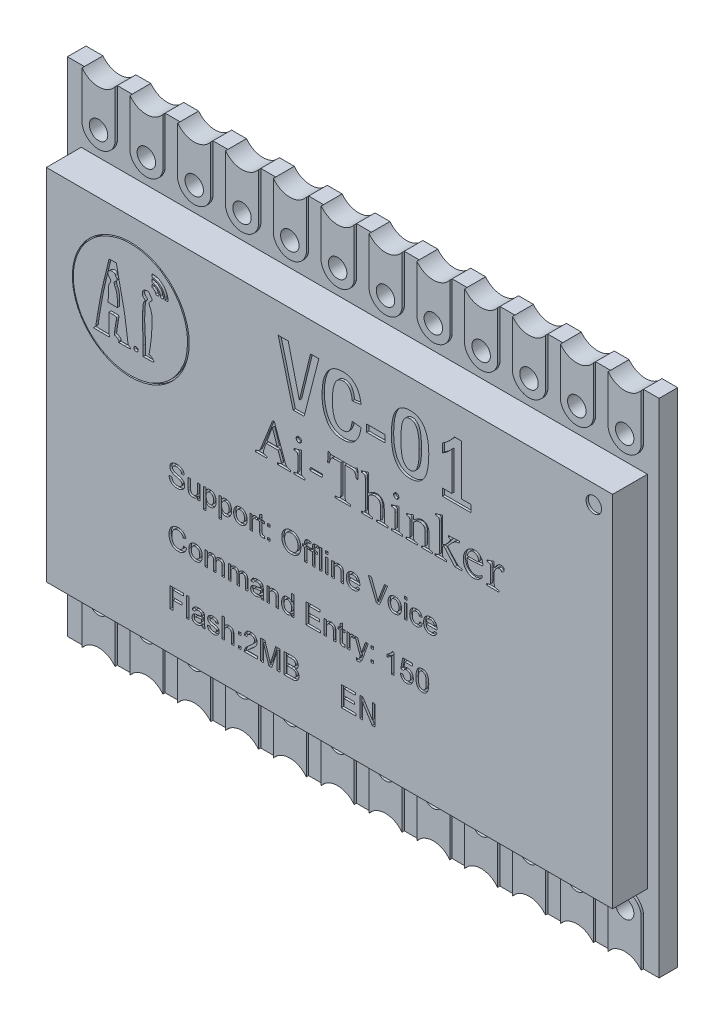
SolidWorks part; units mm, degrees
material "1.4000 (X6Cr13)"
ref_plane "Plan de face" through (0, 0, 0) normal (0, 0, 1) x (1, 0, 0)
ref_plane "Plan de dessus" through (0, 0, 0) normal (0, 1, 0) x (1, 0, 0)
ref_plane "Plan de droite" through (0, 0, 0) normal (1, 0, 0) x (0, 0, -1)
sketch "Esquisse4" plane through (0, 0, 0) normal (0, 0, 1) x (1, 0, 0)
  line L0 (5.9792, 122.5699) -> (31.4792, 122.5699) construction
  line L1 (6.698, 120.6494) -> (30.8117, 120.6494) construction
  line L2 (5.9667, 122.741) -> (6.698, 122.741)
  line L3 (5.9667, 122.741) -> (5.9667, 101.1199)
  line L4 (8.1154, 101.1199) -> (8.758, 101.1199)
  line L5 (31.4487, 122.741) -> (31.4487, 101.1199)
  line L6 (6.698, 122.741) -> (6.698, 120.6494)
  line L7 (8.1154, 122.741) -> (8.1154, 120.6494)
  line L8 (8.1154, 122.741) -> (8.758, 122.741)
  line L9 (10.1754, 122.741) -> (10.1754, 120.6494)
  line L10 (8.758, 122.741) -> (8.758, 120.6494)
  line L11 (12.2354, 122.741) -> (12.2354, 120.6494)
  line L12 (10.818, 122.741) -> (10.818, 120.6494)
  line L13 (14.2954, 122.741) -> (14.2954, 120.6494)
  line L14 (12.878, 122.741) -> (12.878, 120.6494)
  line L15 (16.3554, 122.741) -> (16.3554, 120.6494)
  line L16 (14.938, 122.741) -> (14.938, 120.6494)
  line L17 (18.4154, 122.741) -> (18.4154, 120.6494)
  line L18 (16.998, 122.741) -> (16.998, 120.6494)
  line L19 (20.4754, 122.741) -> (20.4754, 120.6494)
  line L20 (19.058, 122.741) -> (19.058, 120.6494)
  line L21 (22.5354, 122.741) -> (22.5354, 120.6494)
  line L22 (21.118, 122.741) -> (21.118, 120.6494)
  line L23 (24.5954, 122.741) -> (24.5954, 120.6494)
  line L24 (23.178, 122.741) -> (23.178, 120.6494)
  line L25 (26.6554, 122.741) -> (26.6554, 120.6494)
  line L26 (25.238, 122.741) -> (25.238, 120.6494)
  line L27 (28.7154, 122.741) -> (28.7154, 120.6494)
  line L28 (27.298, 122.741) -> (27.298, 120.6494)
  line L29 (30.7754, 122.741) -> (30.7754, 120.6494)
  line L30 (29.358, 122.741) -> (29.358, 120.6494)
  line L31 (10.1754, 122.741) -> (10.818, 122.741)
  line L32 (12.2354, 122.741) -> (12.878, 122.741)
  line L33 (14.2954, 122.741) -> (14.938, 122.741)
  line L34 (16.3554, 122.741) -> (16.998, 122.741)
  line L35 (18.4154, 122.741) -> (19.058, 122.741)
  line L36 (20.4754, 122.741) -> (21.118, 122.741)
  line L37 (22.5354, 122.741) -> (23.178, 122.741)
  line L38 (24.5954, 122.741) -> (25.238, 122.741)
  line L39 (26.6554, 122.741) -> (27.298, 122.741)
  line L40 (28.7154, 122.741) -> (29.358, 122.741)
  line L41 (30.7754, 122.741) -> (31.4487, 122.741)
  line L42 (5.9667, 111.9304) -> (31.4487, 111.9304) construction
  line L43 (8.1154, 101.1199) -> (8.1154, 103.2114)
  line L44 (6.698, 101.1199) -> (6.698, 103.2114)
  line L45 (8.758, 101.1199) -> (8.758, 103.2114)
  line L46 (10.1754, 101.1199) -> (10.1754, 103.2114)
  line L47 (10.818, 101.1199) -> (10.818, 103.2114)
  line L48 (12.2354, 101.1199) -> (12.2354, 103.2114)
  line L49 (12.878, 101.1199) -> (12.878, 103.2114)
  line L50 (14.2954, 101.1199) -> (14.2954, 103.2114)
  line L51 (14.938, 101.1199) -> (14.938, 103.2114)
  line L52 (16.3554, 101.1199) -> (16.3554, 103.2114)
  line L53 (16.998, 101.1199) -> (16.998, 103.2114)
  line L54 (18.4154, 101.1199) -> (18.4154, 103.2114)
  line L55 (19.058, 101.1199) -> (19.058, 103.2114)
  line L56 (20.4754, 101.1199) -> (20.4754, 103.2114)
  line L57 (21.118, 101.1199) -> (21.118, 103.2114)
  line L58 (22.5354, 101.1199) -> (22.5354, 103.2114)
  line L59 (23.178, 101.1199) -> (23.178, 103.2114)
  line L60 (24.5954, 101.1199) -> (24.5954, 103.2114)
  line L61 (25.238, 101.1199) -> (25.238, 103.2114)
  line L62 (26.6554, 101.1199) -> (26.6554, 103.2114)
  line L63 (27.298, 101.1199) -> (27.298, 103.2114)
  line L64 (28.7154, 101.1199) -> (28.7154, 103.2114)
  line L65 (29.358, 101.1199) -> (29.358, 103.2114)
  line L66 (30.7754, 101.1199) -> (30.7754, 103.2114)
  line L67 (10.1754, 101.1199) -> (10.818, 101.1199)
  line L68 (12.2354, 101.1199) -> (12.878, 101.1199)
  line L69 (14.2954, 101.1199) -> (14.938, 101.1199)
  line L70 (16.3554, 101.1199) -> (21.118, 101.1199)
  line L71 (22.5354, 101.1199) -> (23.178, 101.1199)
  line L72 (24.5954, 101.1199) -> (25.238, 101.1199)
  line L73 (26.6554, 101.1199) -> (27.298, 101.1199)
  line L74 (28.7154, 101.1199) -> (29.358, 101.1199)
  line L75 (30.7754, 101.1199) -> (31.4487, 101.1199)
  arc A0 (6.698, 122.741) -> (8.1154, 122.741) centre (7.4067, 123.281) ccw
  arc A1 (6.698, 120.6494) -> (8.1154, 120.6494) centre (7.4067, 120.7811) ccw
  circle A2 centre (7.4067, 120.7811) radius 0.3977
  arc A3 (8.758, 122.741) -> (10.1754, 122.741) centre (9.4667, 123.281) ccw
  arc A4 (8.758, 120.6494) -> (10.1754, 120.6494) centre (9.4667, 120.7811) ccw
  circle A5 centre (9.4667, 120.7811) radius 0.3977
  arc A6 (10.818, 122.741) -> (12.2354, 122.741) centre (11.5267, 123.281) ccw
  arc A7 (10.818, 120.6494) -> (12.2354, 120.6494) centre (11.5267, 120.7811) ccw
  circle A8 centre (11.5267, 120.7811) radius 0.3977
  arc A9 (12.878, 122.741) -> (14.2954, 122.741) centre (13.5867, 123.281) ccw
  arc A10 (12.878, 120.6494) -> (14.2954, 120.6494) centre (13.5867, 120.7811) ccw
  circle A11 centre (13.5867, 120.7811) radius 0.3977
  arc A12 (14.938, 122.741) -> (16.3554, 122.741) centre (15.6467, 123.281) ccw
  arc A13 (14.938, 120.6494) -> (16.3554, 120.6494) centre (15.6467, 120.7811) ccw
  circle A14 centre (15.6467, 120.7811) radius 0.3977
  arc A15 (16.998, 122.741) -> (18.4154, 122.741) centre (17.7067, 123.281) ccw
  arc A16 (16.998, 120.6494) -> (18.4154, 120.6494) centre (17.7067, 120.7811) ccw
  circle A17 centre (17.7067, 120.7811) radius 0.3977
  arc A18 (19.058, 122.741) -> (20.4754, 122.741) centre (19.7667, 123.281) ccw
  arc A19 (19.058, 120.6494) -> (20.4754, 120.6494) centre (19.7667, 120.7811) ccw
  circle A20 centre (19.7667, 120.7811) radius 0.3977
  arc A21 (21.118, 122.741) -> (22.5354, 122.741) centre (21.8267, 123.281) ccw
  arc A22 (21.118, 120.6494) -> (22.5354, 120.6494) centre (21.8267, 120.7811) ccw
  circle A23 centre (21.8267, 120.7811) radius 0.3977
  arc A24 (23.178, 122.741) -> (24.5954, 122.741) centre (23.8867, 123.281) ccw
  arc A25 (23.178, 120.6494) -> (24.5954, 120.6494) centre (23.8867, 120.7811) ccw
  circle A26 centre (23.8867, 120.7811) radius 0.3977
  arc A27 (25.238, 122.741) -> (26.6554, 122.741) centre (25.9467, 123.281) ccw
  arc A28 (25.238, 120.6494) -> (26.6554, 120.6494) centre (25.9467, 120.7811) ccw
  circle A29 centre (25.9467, 120.7811) radius 0.3977
  arc A30 (27.298, 122.741) -> (28.7154, 122.741) centre (28.0067, 123.281) ccw
  arc A31 (27.298, 120.6494) -> (28.7154, 120.6494) centre (28.0067, 120.7811) ccw
  circle A32 centre (28.0067, 120.7811) radius 0.3977
  arc A33 (29.358, 122.741) -> (30.7754, 122.741) centre (30.0667, 123.281) ccw
  arc A34 (29.358, 120.6494) -> (30.7754, 120.6494) centre (30.0667, 120.7811) ccw
  circle A35 centre (30.0667, 120.7811) radius 0.3977
  circle A36 centre (7.4067, 103.0797) radius 0.3977
  arc A37 (6.698, 103.2114) -> (8.1154, 103.2114) centre (7.4067, 103.0797) cw
  arc A38 (6.698, 101.1199) -> (8.1154, 101.1199) centre (7.4067, 100.5799) cw
  arc A39 (8.758, 101.1199) -> (10.1754, 101.1199) centre (9.4667, 100.5799) cw
  arc A40 (8.758, 103.2114) -> (10.1754, 103.2114) centre (9.4667, 103.0797) cw
  circle A41 centre (9.4667, 103.0797) radius 0.3977
  arc A42 (10.818, 101.1199) -> (12.2354, 101.1199) centre (11.5267, 100.5799) cw
  arc A43 (10.818, 103.2114) -> (12.2354, 103.2114) centre (11.5267, 103.0797) cw
  circle A44 centre (11.5267, 103.0797) radius 0.3977
  arc A45 (12.878, 101.1199) -> (14.2954, 101.1199) centre (13.5867, 100.5799) cw
  arc A46 (12.878, 103.2114) -> (14.2954, 103.2114) centre (13.5867, 103.0797) cw
  circle A47 centre (13.5867, 103.0797) radius 0.3977
  arc A48 (14.938, 101.1199) -> (16.3554, 101.1199) centre (15.6467, 100.5799) cw
  arc A49 (14.938, 103.2114) -> (16.3554, 103.2114) centre (15.6467, 103.0797) cw
  circle A50 centre (15.6467, 103.0797) radius 0.3977
  arc A51 (16.998, 101.1199) -> (18.4154, 101.1199) centre (17.7067, 100.5799) cw
  arc A52 (16.998, 103.2114) -> (18.4154, 103.2114) centre (17.7067, 103.0797) cw
  circle A53 centre (17.7067, 103.0797) radius 0.3977
  arc A54 (19.058, 101.1199) -> (20.4754, 101.1199) centre (19.7667, 100.5799) cw
  arc A55 (19.058, 103.2114) -> (20.4754, 103.2114) centre (19.7667, 103.0797) cw
  circle A56 centre (19.7667, 103.0797) radius 0.3977
  arc A57 (21.118, 101.1199) -> (22.5354, 101.1199) centre (21.8267, 100.5799) cw
  arc A58 (21.118, 103.2114) -> (22.5354, 103.2114) centre (21.8267, 103.0797) cw
  circle A59 centre (21.8267, 103.0797) radius 0.3977
  arc A60 (23.178, 101.1199) -> (24.5954, 101.1199) centre (23.8867, 100.5799) cw
  arc A61 (23.178, 103.2114) -> (24.5954, 103.2114) centre (23.8867, 103.0797) cw
  circle A62 centre (23.8867, 103.0797) radius 0.3977
  arc A63 (25.238, 101.1199) -> (26.6554, 101.1199) centre (25.9467, 100.5799) cw
  arc A64 (25.238, 103.2114) -> (26.6554, 103.2114) centre (25.9467, 103.0797) cw
  circle A65 centre (25.9467, 103.0797) radius 0.3977
  arc A66 (27.298, 101.1199) -> (28.7154, 101.1199) centre (28.0067, 100.5799) cw
  arc A67 (27.298, 103.2114) -> (28.7154, 103.2114) centre (28.0067, 103.0797) cw
  circle A68 centre (28.0067, 103.0797) radius 0.3977
  arc A69 (29.358, 101.1199) -> (30.7754, 101.1199) centre (30.0667, 100.5799) cw
  arc A70 (29.358, 103.2114) -> (30.7754, 103.2114) centre (30.0667, 103.0797) cw
  circle A71 centre (30.0667, 103.0797) radius 0.3977
  point P93 (7.4067, 122.39)
  point P101 (7.4067, 101.4709)
  dimension "D1" = 25.5
  dimension "D2" = 12
  dimension "D3" = 12
sketch "Esquisse5" plane through (0, 0, 0) normal (0, 0, 1) x (1, 0, 0)
  line L1 (5.9667, 122.741) -> (31.4487, 122.741)
  line L2 (5.9667, 122.741) -> (5.9667, 101.1199)
  line L3 (5.9667, 101.1199) -> (31.4487, 101.1199)
  line L4 (31.4487, 122.741) -> (31.4487, 101.1199)
sketch "blindage" plane through (0, 0, 0) normal (0, 0, 1) x (1, 0, 0)
  line L1 (6.5603, 119.659) -> (30.9472, 119.659)
  line L2 (6.5603, 119.659) -> (6.5603, 104.1972)
  line L3 (6.5603, 104.1972) -> (30.9472, 104.1972)
  line L4 (30.9472, 119.659) -> (30.9472, 104.1972)
extrude "Boss.-Extru.1" add sketch "blindage" along normal blind 1.5
extrude "Boss.-Extru.2" add sketch "Esquisse5" against normal blind 0.8
extrude "Boss.-Extru.3" add sketch "Esquisse4" along normal blind 0.1 contours L6 A1 L7 A0 A2 | L10 A4 L9 A3 A5 | L12 A7 L11 A6 A8 | L14 A10 L13 A9 A11 | L16 A13 L15 A12 A14 | L18 A16 L17 A15 A17 | L20 A19 L19 A18 A20 | L22 A22 L21 A21 A23 | L24 A25 L23 A24 A26 | L26 A28 L25 A27 A29 | L28 A31 L27 A30 A32 | L30 A34 L29 A33 A35 | L44 A38 L43 A37 A36 | A40 L45 A39 L46 A41 | A43 L47 A42 L48 A44 | A46 L49 A45 L50 A47 | A49 L51 A48 L52 A50 | A52 L53 A51 L54 A53 | A55 L55 A54 L56 A56 | A58 L57 A57 L58 A59 | A61 L59 A60 L60 A62 | A64 L61 A63 L62 A65 | A67 L63 A66 L64 A68 | A70 L65 A69 L66 A71 region at (7.4067, 121.4513, 0) region at (9.4667, 121.4513, 0) region at (11.5267, 121.4513, 0) region at (13.5867, 121.4513, 0) region at (15.6467, 121.4513, 0) region at (17.7067, 121.4513, 0) region at (19.7667, 121.4513, 0) region at (21.8267, 121.4513, 0) region at (23.8867, 121.4513, 0) region at (25.9467, 121.4513, 0) region at (28.0067, 121.4513, 0) region at (30.0667, 121.4513, 0) region at (30.0667, 102.4095, 0) region at (28.0067, 102.4095, 0) region at (25.9467, 102.4095, 0) region at (23.8867, 102.4095, 0) region at (21.8267, 102.4095, 0) region at (19.7667, 102.4095, 0) region at (17.7067, 102.4095, 0) region at (15.6467, 102.4095, 0) region at (13.5867, 102.4095, 0) region at (11.5267, 102.4095, 0) region at (9.4667, 102.4095, 0) region at (7.4067, 102.4095, 0)
sketch "Esquisse7" plane through (0, 0, 0) normal (0, 0, 1) x (1, 0, 0)
  line L0 (6.698, 122.741) -> (8.1154, 122.741)
  line L1 (8.758, 122.741) -> (10.1754, 122.741)
  line L2 (10.818, 122.741) -> (12.2354, 122.741)
  line L3 (12.878, 122.741) -> (14.2954, 122.741)
  line L4 (14.938, 122.741) -> (16.3554, 122.741)
  line L5 (16.998, 122.741) -> (18.4154, 122.741)
  line L6 (19.058, 122.741) -> (20.4754, 122.741)
  line L7 (21.118, 122.741) -> (22.5354, 122.741)
  line L8 (23.178, 122.741) -> (24.5954, 122.741)
  line L9 (25.238, 122.741) -> (26.6554, 122.741)
  line L10 (27.298, 122.741) -> (28.7154, 122.741)
  line L11 (29.358, 122.741) -> (30.7754, 122.741)
  line L12 (5.9667, 111.9304) -> (31.4487, 111.9304) construction
  line L13 (5.9667, 122.741) -> (5.9667, 101.1199) construction
  line L14 (31.4487, 101.1199) -> (31.4487, 122.741) construction
  line L15 (29.358, 101.1199) -> (30.7754, 101.1199)
  line L16 (27.298, 101.1199) -> (28.7154, 101.1199)
  line L17 (25.238, 101.1199) -> (26.6554, 101.1199)
  line L18 (23.178, 101.1199) -> (24.5954, 101.1199)
  line L19 (21.118, 101.1199) -> (22.5354, 101.1199)
  line L20 (19.058, 101.1199) -> (20.4754, 101.1199)
  line L21 (16.998, 101.1199) -> (18.4154, 101.1199)
  line L22 (14.938, 101.1199) -> (16.3554, 101.1199)
  line L23 (12.878, 101.1199) -> (14.2954, 101.1199)
  line L24 (10.818, 101.1199) -> (12.2354, 101.1199)
  line L25 (8.758, 101.1199) -> (10.1754, 101.1199)
  line L26 (6.698, 101.1199) -> (8.1154, 101.1199)
  arc A0 (6.698, 122.741) -> (8.1154, 122.741) centre (7.4067, 123.281) ccw
  circle A1 centre (7.4067, 120.7811) radius 0.3977
  circle A2 centre (9.4667, 120.7811) radius 0.3977
  arc A3 (8.758, 122.741) -> (10.1754, 122.741) centre (9.4667, 123.281) ccw
  circle A4 centre (11.5267, 120.7811) radius 0.3977
  arc A5 (10.818, 122.741) -> (12.2354, 122.741) centre (11.5267, 123.281) ccw
  circle A6 centre (13.5867, 120.7811) radius 0.3977
  arc A7 (12.878, 122.741) -> (14.2954, 122.741) centre (13.5867, 123.281) ccw
  circle A8 centre (15.6467, 120.7811) radius 0.3977
  arc A9 (14.938, 122.741) -> (16.3554, 122.741) centre (15.6467, 123.281) ccw
  circle A10 centre (17.7067, 120.7811) radius 0.3977
  arc A11 (16.998, 122.741) -> (18.4154, 122.741) centre (17.7067, 123.281) ccw
  circle A12 centre (19.7667, 120.7811) radius 0.3977
  arc A13 (19.058, 122.741) -> (20.4754, 122.741) centre (19.7667, 123.281) ccw
  circle A14 centre (21.8267, 120.7811) radius 0.3977
  arc A15 (21.118, 122.741) -> (22.5354, 122.741) centre (21.8267, 123.281) ccw
  circle A16 centre (23.8867, 120.7811) radius 0.3977
  arc A17 (23.178, 122.741) -> (24.5954, 122.741) centre (23.8867, 123.281) ccw
  circle A18 centre (25.9467, 120.7811) radius 0.3977
  arc A19 (25.238, 122.741) -> (26.6554, 122.741) centre (25.9467, 123.281) ccw
  circle A20 centre (28.0067, 120.7811) radius 0.3977
  arc A21 (27.298, 122.741) -> (28.7154, 122.741) centre (28.0067, 123.281) ccw
  circle A22 centre (30.0667, 120.7811) radius 0.3977
  arc A23 (29.358, 122.741) -> (30.7754, 122.741) centre (30.0667, 123.281) ccw
  arc A24 (29.358, 101.1199) -> (30.7754, 101.1199) centre (30.0667, 100.5799) cw
  circle A25 centre (30.0667, 103.0797) radius 0.3977
  arc A26 (27.298, 101.1199) -> (28.7154, 101.1199) centre (28.0067, 100.5799) cw
  circle A27 centre (28.0067, 103.0797) radius 0.3977
  arc A28 (25.238, 101.1199) -> (26.6554, 101.1199) centre (25.9467, 100.5799) cw
  circle A29 centre (25.9467, 103.0797) radius 0.3977
  arc A30 (23.178, 101.1199) -> (24.5954, 101.1199) centre (23.8867, 100.5799) cw
  circle A31 centre (23.8867, 103.0797) radius 0.3977
  arc A32 (21.118, 101.1199) -> (22.5354, 101.1199) centre (21.8267, 100.5799) cw
  circle A33 centre (21.8267, 103.0797) radius 0.3977
  arc A34 (19.058, 101.1199) -> (20.4754, 101.1199) centre (19.7667, 100.5799) cw
  circle A35 centre (19.7667, 103.0797) radius 0.3977
  arc A36 (16.998, 101.1199) -> (18.4154, 101.1199) centre (17.7067, 100.5799) cw
  circle A37 centre (17.7067, 103.0797) radius 0.3977
  arc A38 (14.938, 101.1199) -> (16.3554, 101.1199) centre (15.6467, 100.5799) cw
  circle A39 centre (15.6467, 103.0797) radius 0.3977
  arc A40 (12.878, 101.1199) -> (14.2954, 101.1199) centre (13.5867, 100.5799) cw
  circle A41 centre (13.5867, 103.0797) radius 0.3977
  arc A42 (10.818, 101.1199) -> (12.2354, 101.1199) centre (11.5267, 100.5799) cw
  circle A43 centre (11.5267, 103.0797) radius 0.3977
  arc A44 (8.758, 101.1199) -> (10.1754, 101.1199) centre (9.4667, 100.5799) cw
  circle A45 centre (9.4667, 103.0797) radius 0.3977
  circle A46 centre (7.4067, 103.0797) radius 0.3977
  arc A47 (6.698, 101.1199) -> (8.1154, 101.1199) centre (7.4067, 100.5799) cw
  dimension "D1" = 12
extrude "Enlèv. mat.-Extru.1" cut sketch "Esquisse7" against normal through all both and the other way through all
sketch "Esquisse9" plane through (-2.3595, 4.3629, 1.5) normal (0, 0, 1) x (1, 0, 0)
  line L0 (11.6221, 110.7844) -> (11.6144, 111.2429)
  line L1 (11.6144, 111.2429) -> (11.7786, 111.2429)
  line L2 (12.0435, 110.3667) -> (12.0357, 110.3259)
  line L3 (12.0357, 110.3259) -> (12.2989, 110.3259)
  line L4 (11.9577, 113.1255) -> (11.9375, 113.2357)
  line L5 (11.9375, 113.2357) -> (11.7769, 113.2357)
  line L6 (11.7769, 113.2357) -> (11.6164, 113.2357)
  line L7 (11.6164, 113.2357) -> (11.5746, 113.0461)
  line L8 (11.2924, 110.3259) -> (11.6297, 110.3259)
  line L9 (11.6297, 110.3259) -> (11.6221, 110.7844)
  line L10 (11.978, 111.8058) -> (11.978, 111.5956)
  line L11 (11.978, 111.5956) -> (11.7737, 111.5956)
  line L12 (11.7737, 111.5956) -> (11.5695, 111.5956)
  line L13 (11.5695, 111.5956) -> (11.5835, 111.7147)
  line L14 (13.0882, 110.7447) -> (13.089, 110.3259)
  line L15 (13.089, 110.3259) -> (13.3182, 110.3259)
  line L16 (13.5814, 113.601) -> (13.4593, 113.6112)
  line L17 (13.4593, 113.6112) -> (13.4593, 113.5494)
  line L18 (14.0189, 112.9932) -> (14.0286, 112.9006)
  line L19 (14.0286, 112.9006) -> (14.0967, 112.9006)
  line L20 (12.5423, 114.2629) -> (12.5696, 109.3487) construction
  line L21 (10.0867, 111.8072) -> (14.9989, 111.8542) construction
  circle A0 centre (12.5559, 111.8058) radius 2.516
  spline S0 degree 3 poles (12.3218, 109.3574) (12.178, 109.3697) (12.1, 109.3841) (11.8545, 109.4436) knots 0 0 0 0 1 1 1 1
  spline S1 degree 3 poles (11.8545, 109.4436) (11.704, 109.48) (11.3088, 109.6625) (11.1937, 109.7487) knots 0 0 0 0 1 1 1 1
  spline S2 degree 3 poles (11.1937, 109.7487) (11.1649, 109.7703) (11.0895, 109.8268) (11.0262, 109.8742) knots 0 0 0 0 1 1 1 1
  spline S3 degree 3 poles (11.0262, 109.8742) (10.8716, 109.99) (10.7052, 110.1617) (10.5711, 110.3435) knots 0 0 0 0 1 1 1 1
  spline S4 degree 3 poles (10.5711, 110.3435) (10.5104, 110.4259) (10.4535, 110.5022) (10.4449, 110.513) knots 0 0 0 0 1 1 1 1
  spline S5 degree 3 poles (10.4449, 110.513) (10.4132, 110.5526) (10.2524, 110.902) (10.2186, 111.0048) knots 0 0 0 0 1 1 1 1
  spline S6 degree 3 poles (10.2186, 111.0048) (10.1118, 111.3298) (10.0867, 111.4828) (10.0867, 111.8072) knots 0 0 0 0 1 1 1 1
  spline S7 degree 3 poles (10.0867, 111.8072) (10.0867, 112.1317) (10.1118, 112.2847) (10.2186, 112.6097) knots 0 0 0 0 1 1 1 1
  spline S8 degree 3 poles (10.2186, 112.6097) (10.2602, 112.7362) (10.4198, 113.0733) (10.4545, 113.108) knots 0 0 0 0 1 1 1 1
  spline S9 degree 3 poles (10.4545, 113.108) (10.4681, 113.1216) (10.4883, 113.1499) (10.4994, 113.171) knots 0 0 0 0 1 1 1 1
  spline S10 degree 3 poles (10.4994, 113.171) (10.5942, 113.3508) (10.9987, 113.7553) (11.1786, 113.8502) knots 0 0 0 0 1 1 1 1
  spline S11 degree 3 poles (11.1786, 113.8502) (11.1996, 113.8613) (11.228, 113.8815) (11.2415, 113.895) knots 0 0 0 0 1 1 1 1
  spline S12 degree 3 poles (11.2415, 113.895) (11.2763, 113.9298) (11.6133, 114.0893) (11.7399, 114.1309) knots 0 0 0 0 1 1 1 1
  spline S13 degree 3 poles (11.7399, 114.1309) (12.0649, 114.2377) (12.2179, 114.2629) (12.5423, 114.2629) knots 0 0 0 0 1 1 1 1
  spline S14 degree 3 poles (12.5423, 114.2629) (12.8667, 114.2629) (13.0197, 114.2377) (13.3447, 114.1309) knots 0 0 0 0 1 1 1 1
  spline S15 degree 3 poles (13.3447, 114.1309) (13.4475, 114.0971) (13.797, 113.9363) (13.8365, 113.9047) knots 0 0 0 0 1 1 1 1
  spline S16 degree 3 poles (13.8365, 113.9047) (13.8473, 113.896) (13.9236, 113.8392) (14.006, 113.7784) knots 0 0 0 0 1 1 1 1
  spline S17 degree 3 poles (14.006, 113.7784) (14.1879, 113.6444) (14.3595, 113.4779) (14.4753, 113.3234) knots 0 0 0 0 1 1 1 1
  spline S18 degree 3 poles (14.4753, 113.3234) (14.5227, 113.26) (14.5792, 113.1846) (14.6008, 113.1558) knots 0 0 0 0 1 1 1 1
  spline S19 degree 3 poles (14.6008, 113.1558) (14.687, 113.0407) (14.8695, 112.6455) (14.906, 112.495) knots 0 0 0 0 1 1 1 1
  spline S20 degree 3 poles (14.906, 112.495) (14.9638, 112.2563) (14.979, 112.1691) (14.9928, 111.9968) knots 0 0 0 0 1 1 1 1
  spline S21 degree 3 poles (14.9928, 111.9968) (15.019, 111.6686) (14.9598, 111.2163) (14.8583, 110.9696) knots 0 0 0 0 1 1 1 1
  spline S22 degree 3 poles (14.8583, 110.9696) (14.6504, 110.4643) (14.3879, 110.1176) (13.9884, 109.8205) knots 0 0 0 0 1 1 1 1
  spline S23 degree 3 poles (13.9884, 109.8205) (13.7936, 109.6757) (13.4158, 109.4845) (13.2628, 109.4533) knots 0 0 0 0 1 1 1 1
  spline S24 degree 3 poles (13.2628, 109.4533) (13.2302, 109.4466) (13.1798, 109.4343) (13.1507, 109.4259) knots 0 0 0 0 1 1 1 1
  spline S25 degree 3 poles (13.1507, 109.4259) (12.921, 109.3592) (12.6044, 109.3331) (12.3218, 109.3574) knots 0 0 0 0 1 1 1 1
  spline S26 degree 3 poles (11.7786, 111.2429) (11.9666, 111.2429) (11.9584, 111.2535) (11.9238, 111.0577) knots 0 0 0 0 1 1 1 1
  spline S27 degree 3 poles (11.9238, 111.0577) (11.9135, 110.9995) (11.8976, 110.9003) (11.8886, 110.8373) knots 0 0 0 0 1 1 1 1
  spline S28 degree 3 poles (11.8886, 110.8373) (11.8795, 110.7742) (11.8652, 110.679) (11.8567, 110.6257) knots 0 0 0 0 1 1 1 1
  spline S29 degree 3 poles (11.8567, 110.6257) (11.8399, 110.5198) (11.8435, 110.5022) (11.8824, 110.5022) knots 0 0 0 0 1 1 1 1
  spline S30 degree 3 poles (11.8824, 110.5022) (11.8966, 110.5022) (11.9404, 110.4809) (11.9798, 110.4548) knots 0 0 0 0 1 1 1 1
  spline S31 degree 3 poles (11.9798, 110.4548) (12.0363, 110.4174) (12.0497, 110.3989) (12.0435, 110.3667) knots 0 0 0 0 1 1 1 1
  spline S32 degree 3 poles (12.2989, 110.3259) (12.5806, 110.3259) (12.5847, 110.3277) (12.4876, 110.4094) knots 0 0 0 0 1 1 1 1
  spline S33 degree 3 poles (12.4876, 110.4094) (12.4568, 110.4353) (12.4371, 110.4725) (12.4314, 110.5155) knots 0 0 0 0 1 1 1 1
  spline S34 degree 3 poles (12.4314, 110.5155) (12.4266, 110.5518) (12.4055, 110.7125) (12.3845, 110.8726) knots 0 0 0 0 1 1 1 1
  spline S35 degree 3 poles (12.3845, 110.8726) (12.3252, 111.3241) (12.2634, 111.7071) (12.2251, 111.8602) knots 0 0 0 0 1 1 1 1
  spline S36 degree 3 poles (12.2251, 111.8602) (12.2166, 111.8941) (12.1965, 111.9854) (12.1804, 112.063) knots 0 0 0 0 1 1 1 1
  spline S37 degree 3 poles (12.1804, 112.063) (12.1508, 112.2059) (12.105, 112.4203) (12.0562, 112.6449) knots 0 0 0 0 1 1 1 1
  spline S38 degree 3 poles (12.0562, 112.6449) (12.0118, 112.8493) (11.979, 113.0091) (11.9577, 113.1255) knots 0 0 0 0 1 1 1 1
  spline S39 degree 3 poles (11.5746, 113.0461) (11.5515, 112.9419) (11.5262, 112.8328) (11.5184, 112.8037) knots 0 0 0 0 1 1 1 1
  spline S40 degree 3 poles (11.5184, 112.8037) (11.4748, 112.6428) (11.4239, 112.437) (11.4028, 112.3363) knots 0 0 0 0 1 1 1 1
  spline S41 degree 3 poles (11.4028, 112.3363) (11.3896, 112.2733) (11.3664, 112.1701) (11.3512, 112.1071) knots 0 0 0 0 1 1 1 1
  spline S42 degree 3 poles (11.3512, 112.1071) (11.3361, 112.044) (11.3123, 111.9369) (11.2985, 111.869) knots 0 0 0 0 1 1 1 1
  spline S43 degree 3 poles (11.2985, 111.869) (11.2846, 111.8011) (11.2607, 111.686) (11.2453, 111.6133) knots 0 0 0 0 1 1 1 1
  spline S44 degree 3 poles (11.2453, 111.6133) (11.1971, 111.3858) (11.1828, 111.3036) (11.1298, 110.9519) knots 0 0 0 0 1 1 1 1
  spline S45 degree 3 poles (11.1298, 110.9519) (11.1108, 110.8258) (11.0876, 110.6844) (11.0781, 110.6376) knots 0 0 0 0 1 1 1 1
  spline S46 degree 3 poles (11.0781, 110.6376) (11.0686, 110.5907) (11.0609, 110.5285) (11.0609, 110.4991) knots 0 0 0 0 1 1 1 1
  spline S47 degree 3 poles (11.0609, 110.4991) (11.0609, 110.4626) (11.0442, 110.4302) (11.008, 110.3964) knots 0 0 0 0 1 1 1 1
  spline S48 degree 3 poles (11.008, 110.3964) (10.9789, 110.3692) (10.9551, 110.3422) (10.9551, 110.3364) knots 0 0 0 0 1 1 1 1
  spline S49 degree 3 poles (10.9551, 110.3364) (10.9551, 110.3306) (11.1069, 110.3259) (11.2924, 110.3259) knots 0 0 0 0 1 1 1 1
  spline S50 degree 3 poles (11.5835, 111.7147) (11.5912, 111.7801) (11.596, 111.917) (11.5941, 112.0189) knots 0 0 0 0 1 1 1 1
  spline S51 degree 3 poles (11.5941, 112.0189) (11.5905, 112.2105) (11.6067, 112.2941) (11.663, 112.3743) knots 0 0 0 0 1 1 1 1
  spline S52 degree 3 poles (11.663, 112.3743) (11.7105, 112.442) (11.7037, 112.4835) (11.6341, 112.5532) knots 0 0 0 0 1 1 1 1
  spline S53 degree 3 poles (11.6341, 112.5532) (11.545, 112.6423) (11.5522, 112.751) (11.6514, 112.8123) knots 0 0 0 0 1 1 1 1
  spline S54 degree 3 poles (11.6514, 112.8123) (11.7548, 112.8762) (11.8898, 112.8441) (11.8898, 112.7557) knots 0 0 0 0 1 1 1 1
  spline S55 degree 3 poles (11.8898, 112.7557) (11.8898, 112.7405) (11.9017, 112.7235) (11.9164, 112.7179) knots 0 0 0 0 1 1 1 1
  spline S56 degree 3 poles (11.9164, 112.7179) (11.931, 112.7122) (11.9521, 112.6877) (11.9631, 112.6634) knots 0 0 0 0 1 1 1 1
  spline S57 degree 3 poles (11.9631, 112.6634) (11.9816, 112.6229) (11.977, 112.6136) (11.9084, 112.5535) knots 0 0 0 0 1 1 1 1
  spline S58 degree 3 poles (11.9084, 112.5535) (11.8389, 112.4926) (11.8343, 112.483) (11.8442, 112.4211) knots 0 0 0 0 1 1 1 1
  spline S59 degree 3 poles (11.8442, 112.4211) (11.85, 112.3844) (11.8699, 112.3276) (11.8883, 112.2948) knots 0 0 0 0 1 1 1 1
  spline S60 degree 3 poles (11.8883, 112.2948) (11.9488, 112.1871) (11.978, 112.0282) (11.978, 111.8058) knots 0 0 0 0 1 1 1 1
  spline S61 degree 3 poles (13.5475, 110.3668) (13.5475, 110.422) (13.4281, 110.5199) (13.3607, 110.5199) knots 0 0 0 0 1 1 1 1
  spline S62 degree 3 poles (13.3607, 110.5199) (13.3408, 110.5199) (13.3357, 110.5292) (13.3438, 110.5504) knots 0 0 0 0 1 1 1 1
  spline S63 degree 3 poles (13.3438, 110.5504) (13.3615, 110.5964) (13.4219, 111.0046) (13.4444, 111.2296) knots 0 0 0 0 1 1 1 1
  spline S64 degree 3 poles (13.4444, 111.2296) (13.4553, 111.3388) (13.4676, 111.5575) (13.4718, 111.7157) knots 0 0 0 0 1 1 1 1
  spline S65 degree 3 poles (13.4718, 111.7157) (13.48, 112.0285) (13.4637, 112.1364) (13.3793, 112.3272) knots 0 0 0 0 1 1 1 1
  spline S66 degree 3 poles (13.3793, 112.3272) (13.3554, 112.3813) (13.3359, 112.4362) (13.3359, 112.4493) knots 0 0 0 0 1 1 1 1
  spline S67 degree 3 poles (13.3359, 112.4493) (13.3359, 112.4624) (13.3676, 112.501) (13.4064, 112.535) knots 0 0 0 0 1 1 1 1
  spline S68 degree 3 poles (13.4064, 112.535) (13.4861, 112.6048) (13.4931, 112.638) (13.4403, 112.6942) knots 0 0 0 0 1 1 1 1
  spline S69 degree 3 poles (13.4403, 112.6942) (13.4202, 112.7156) (13.3931, 112.7581) (13.3802, 112.7887) knots 0 0 0 0 1 1 1 1
  spline S70 degree 3 poles (13.3802, 112.7887) (13.3529, 112.8536) (13.3072, 112.8726) (13.2161, 112.8571) knots 0 0 0 0 1 1 1 1
  spline S71 degree 3 poles (13.2161, 112.8571) (13.1183, 112.8405) (13.0705, 112.796) (13.0591, 112.7111) knots 0 0 0 0 1 1 1 1
  spline S72 degree 3 poles (13.0591, 112.7111) (13.0453, 112.6081) (13.0635, 112.5546) (13.1244, 112.5186) knots 0 0 0 0 1 1 1 1
  spline S73 degree 3 poles (13.1244, 112.5186) (13.1765, 112.4878) (13.1939, 112.4369) (13.1594, 112.4156) knots 0 0 0 0 1 1 1 1
  spline S74 degree 3 poles (13.1594, 112.4156) (13.1007, 112.3793) (13.0809, 112.2876) (13.0663, 111.9836) knots 0 0 0 0 1 1 1 1
  spline S75 degree 3 poles (13.0663, 111.9836) (13.0465, 111.5708) (13.0465, 111.5616) (13.0684, 111.3487) knots 0 0 0 0 1 1 1 1
  spline S76 degree 3 poles (13.0684, 111.3487) (13.0789, 111.2469) (13.0878, 110.9751) (13.0882, 110.7447) knots 0 0 0 0 1 1 1 1
  spline S77 degree 3 poles (13.3182, 110.3259) (13.5463, 110.3259) (13.5475, 110.3261) (13.5475, 110.3668) knots 0 0 0 0 1 1 1 1
  spline S78 degree 3 poles (12.8629, 110.4052) (12.8935, 110.4723) (12.858, 110.5375) (12.7908, 110.5375) knots 0 0 0 0 1 1 1 1
  spline S79 degree 3 poles (12.7908, 110.5375) (12.7027, 110.5375) (12.661, 110.4711) (12.7016, 110.3952) knots 0 0 0 0 1 1 1 1
  spline S80 degree 3 poles (12.7016, 110.3952) (12.7303, 110.3417) (12.837, 110.3483) (12.8629, 110.4052) knots 0 0 0 0 1 1 1 1
  spline S81 degree 3 poles (13.7715, 112.93) (13.778, 112.9469) (13.7624, 112.9983) (13.735, 113.0506) knots 0 0 0 0 1 1 1 1
  spline S82 degree 3 poles (13.735, 113.0506) (13.6836, 113.1488) (13.5886, 113.2181) (13.5054, 113.2181) knots 0 0 0 0 1 1 1 1
  spline S83 degree 3 poles (13.5054, 113.2181) (13.4645, 113.2181) (13.4593, 113.2112) (13.4593, 113.1564) knots 0 0 0 0 1 1 1 1
  spline S84 degree 3 poles (13.4593, 113.1564) (13.4593, 113.1115) (13.4671, 113.0946) (13.4875, 113.0946) knots 0 0 0 0 1 1 1 1
  spline S85 degree 3 poles (13.4875, 113.0946) (13.5285, 113.0946) (13.6357, 112.9811) (13.6357, 112.9377) knots 0 0 0 0 1 1 1 1
  spline S86 degree 3 poles (13.6357, 112.9377) (13.6357, 112.9071) (13.6465, 112.9006) (13.698, 112.9006) knots 0 0 0 0 1 1 1 1
  spline S87 degree 3 poles (13.698, 112.9006) (13.7398, 112.9006) (13.7639, 112.9103) (13.7715, 112.93) knots 0 0 0 0 1 1 1 1
  spline S88 degree 3 poles (13.9708, 112.9304) (13.9708, 112.9467) (13.9573, 113.0082) (13.9409, 113.067) knots 0 0 0 0 1 1 1 1
  spline S89 degree 3 poles (13.9409, 113.067) (13.917, 113.1524) (13.8929, 113.1918) (13.8218, 113.2622) knots 0 0 0 0 1 1 1 1
  spline S90 degree 3 poles (13.8218, 113.2622) (13.7318, 113.3512) (13.6962, 113.3731) (13.5815, 113.4096) knots 0 0 0 0 1 1 1 1
  spline S91 degree 3 poles (13.5815, 113.4096) (13.4742, 113.4438) (13.4593, 113.4379) (13.4593, 113.3611) knots 0 0 0 0 1 1 1 1
  spline S92 degree 3 poles (13.4593, 113.3611) (13.4593, 113.2963) (13.4628, 113.2919) (13.5232, 113.2806) knots 0 0 0 0 1 1 1 1
  spline S93 degree 3 poles (13.5232, 113.2806) (13.6821, 113.2508) (13.8297, 113.0937) (13.8297, 112.9543) knots 0 0 0 0 1 1 1 1
  spline S94 degree 3 poles (13.8297, 112.9543) (13.8297, 112.9035) (13.8334, 112.9006) (13.9002, 112.9006) knots 0 0 0 0 1 1 1 1
  spline S95 degree 3 poles (13.9002, 112.9006) (13.9546, 112.9006) (13.9708, 112.9075) (13.9708, 112.9304) knots 0 0 0 0 1 1 1 1
  spline S96 degree 3 poles (14.1646, 112.958) (14.1643, 113.0278) (14.1271, 113.1544) (14.0798, 113.2466) knots 0 0 0 0 1 1 1 1
  spline S97 degree 3 poles (14.0798, 113.2466) (14.0246, 113.3541) (13.9412, 113.4406) (13.8175, 113.5187) knots 0 0 0 0 1 1 1 1
  spline S98 degree 3 poles (13.8175, 113.5187) (13.7214, 113.5794) (13.6843, 113.5923) (13.5814, 113.601) knots 0 0 0 0 1 1 1 1
  spline S99 degree 3 poles (13.4593, 113.5494) (13.4593, 113.4884) (13.4606, 113.4874) (13.5463, 113.4772) knots 0 0 0 0 1 1 1 1
  spline S100 degree 3 poles (13.5463, 113.4772) (13.7815, 113.4494) (13.994, 113.2317) (14.0189, 112.9932) knots 0 0 0 0 1 1 1 1
  spline S101 degree 3 poles (14.0967, 112.9006) (14.1618, 112.9006) (14.1647, 112.9032) (14.1646, 112.958) knots 0 0 0 0 1 1 1 1
extrude "Enlèv. mat.-Extru.2" cut sketch "Esquisse9" against normal blind 0.1 contours A0 S24 S25 S0 S1 S2 S3 S4 S5 S6 S7 S8 S9 S10 S11 S12 S13 S14 S15 S16 S17 S18 S19 S20 S21 S22 S23 | L19 S101 S96 S97 S98 L16 L17 S99 S100 L18 | S94 S95 S88 S89 S90 S91 S92 S93 | S86 S87 S81 S82 S83 S84 S85 | L15 S77 S61 S62 S63 S64 S65 S66 S67 S68 S69 S70 S71 S72 S73 S74 S75 S76 L14 | S48 S49 L8 L9 L0 L1 S26 S27 S28 S29 S30 S31 L2 L3 S32 S33 S34 S35 S36 S37 S38 L4 L5 L6 L7 S39 S40 S41 S42 S43 S44 S45 S46 S47 S59 S60 L10 L11 L12 L13 S50 S51 S52 S53 S54 S55 S56 S57 S58 | S79 S80 S78 region at (9.3924, 115.8017, 1.5) region at (10.8986, 115.9367, 1.5) region at (11.5149, 117.6734, 1.5) region at (7.6875, 116.1687, 1.5) region at (10.4208, 114.8113, 1.5) region at (11.2624, 117.4293, 1.5) region at (11.3829, 117.5562, 1.5)
sketch "Esquisse11" plane through (0, 0, 1.5) normal (0, 0, 1) x (1, 0, 0)
  text T0 "VC-01" font "Franklin Gothic Medium Cond" height in points 10
extrude "Enlèv. mat.-Extru.3" cut sketch "Esquisse11" against normal blind 0.1
sketch "Esquisse12" plane through (0, 0, 1.5) normal (0, 0, 1) x (1, 0, 0)
  text T0 "Ai-Thinker" font "Adobe Devanagari" height in points 6
extrude "Enlèv. mat.-Extru.4" cut sketch "Esquisse12" against normal blind 0.1
sketch "Esquisse13" plane through (0, 0, 1.5) normal (0, 0, 1) x (1, 0, 0)
  text T0 "Support: Offline Voice\r\nCommand Entry: 150\r\nFlash:2MB     EN\r\n" font "Century Gothic" height in points 4
extrude "Enlèv. mat.-Extru.5" cut sketch "Esquisse13" against normal blind 0.1
sketch "Esquisse14" plane through (0, 0, 1.5) normal (0, 0, 1) x (1, 0, 0)
  circle A0 centre (30.1396, 118.8681) radius 0.3345
extrude "Enlèv. mat.-Extru.6" cut sketch "Esquisse14" against normal blind 0.1
